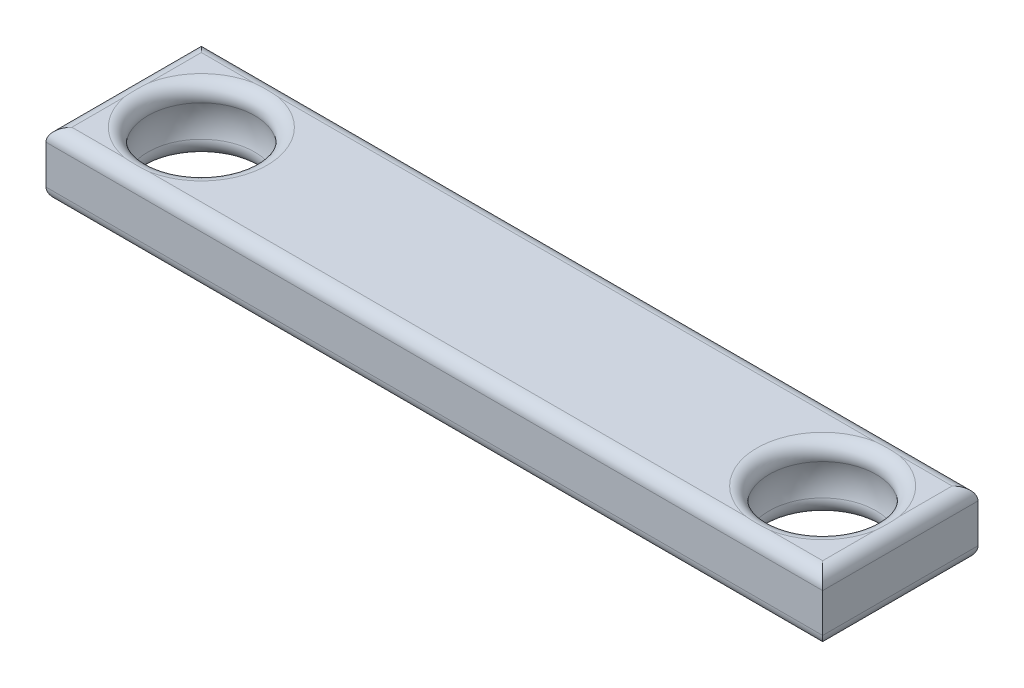
SolidWorks part; units mm, degrees
ref_plane "Front Plane" through (0, 0, 0) normal (0, 0, 1) x (1, 0, 0)
ref_plane "Top Plane" through (0, 0, 0) normal (0, 1, 0) x (1, 0, 0)
ref_plane "Right Plane" through (0, 0, 0) normal (1, 0, 0) x (0, 0, -1)
sketch "Sketch1" plane through (0, 0, 0) normal (0, 0, 1) x (1, 0, 0)
  line L1 (-30, 2.5) -> (30, 2.5)
  line L2 (-30, 2.5) -> (-30, -2.5)
  line L3 (-30, -2.5) -> (30, -2.5)
  line L4 (30, 2.5) -> (30, -2.5)
  line L5 (-30, 2.5) -> (30, -2.5) construction
  line L6 (-30, -2.5) -> (30, 2.5) construction
  point P0 (0, 0)
  dimension "D1" = 60
  dimension "D2" = 5
extrude "Boss-Extrude1" add sketch "Sketch1" along normal mid plane 12
sketch "Sketch2" plane through (0, 0, 0) normal (0, 0, 1) x (1, 0, 0)
  line L0 (-24, 2.5) -> (-24, -2.5)
  line L1 (30, 2.5) -> (-30, 2.5) construction
  line L2 (-30, -2.5) -> (30, -2.5) construction
  line L3 (-27.5, 2.5) -> (-24, 2.5)
  line L4 (-24, -2.5) -> (-27.5, -2.5)
  line L5 (-30, 2.5) -> (-30, -2.5) construction
  arc A0 (-27.5, 2.5) -> (-27.5, -2.5) centre (-24, 0) ccw
  dimension "D1" = 3.5
  dimension "D2" = 3.5
  dimension "D3" = 6
revolve "Cut-Revolve1" cut sketch "Sketch2" angle 360 about L0
mirror "Mirror1" about plane through (0, 0, 0) normal (1, 0, 0) of "Cut-Revolve1"
fillet "Fillet1" radius 1 12 edges at (-30, -2.5, 0) (0, -2.5, 6) (30, -2.5, 0) (0, -2.5, -6) (-27.5, -2.5, 0) (27.5, -2.5, 0) (30, 2.5, 0) (0, 2.5, 6) (-30, 2.5, 0) (0, 2.5, -6) (-27.5, 2.5, 0) (27.5, 2.5, 0)
